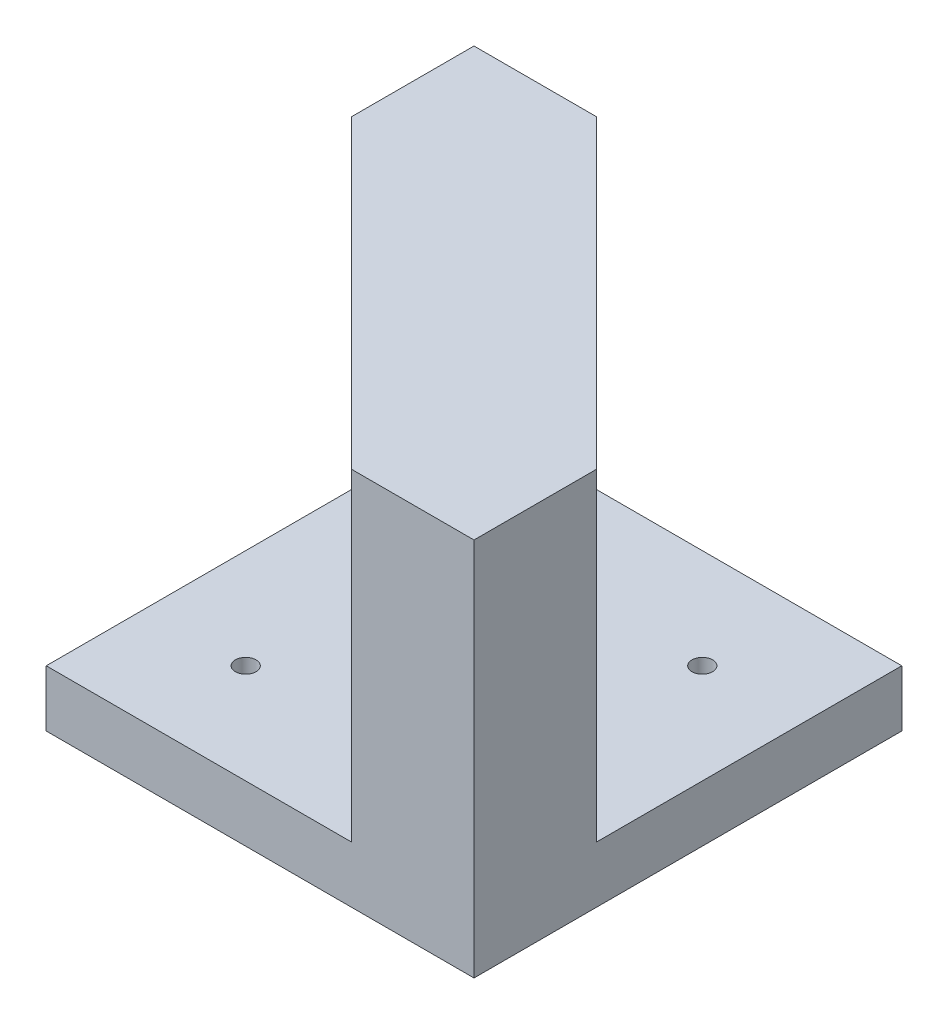
SolidWorks part; units mm, degrees
ref_plane "Front Plane" through (0, 0, 0) normal (0, 0, 1) x (1, 0, 0)
ref_plane "Top Plane" through (0, 0, 0) normal (0, 1, 0) x (1, 0, 0)
ref_plane "Right Plane" through (0, 0, 0) normal (1, 0, 0) x (0, 0, -1)
sketch "Sketch1" plane through (0, 0, 0) normal (0, 1, 0) x (1, 0, 0)
  line L1 (-33.655, 33.655) -> (33.655, 33.655)
  line L2 (-33.655, 33.655) -> (-33.655, -33.655)
  line L3 (-33.655, -33.655) -> (33.655, -33.655)
  line L4 (33.655, 33.655) -> (33.655, -33.655)
  line L5 (-33.655, 33.655) -> (33.655, -33.655) construction
  line L6 (-33.655, -33.655) -> (33.655, 33.655) construction
  circle A0 centre (17.9605, 17.9605) radius 1.625
  circle A2 centre (-17.9605, -17.9605) radius 1.625
  circle A4 centre (-17.9605, 17.9605) radius 1.625 [skipped]
  circle A5 centre (17.9605, -17.9605) radius 1.625 [skipped]
  point P0 (0, 0)
  point P6 (0, 0)
  point P7 (16.0068, 25.6922)
  point P8 (0, 0)
  point P11 (0, 0)
  point P12 (0, 0)
  point P15 (0, 0)
  point P20 (0, 0)
  dimension "D1" = 3.25
  dimension "D2" = 25.4
  dimension "D4" = 67.31
  dimension "D3" = 4
extrude "Boss-Extrude1" add sketch "Sketch1" along normal blind 8.89
sketch "Sketch2" plane through (0, 8.89, 0) normal (0, 1, 0) x (1, 0, 0)
  line L0 (-26.9233, 33.655) -> (33.655, -26.9233)
  line L1 (33.655, -26.9233) -> (33.655, -14.351)
  line L2 (33.655, -14.351) -> (-14.351, 33.655)
  line L3 (-14.351, 33.655) -> (-26.9233, 33.655)
  line L6 (26.9233, -33.655) -> (-33.655, 26.9233)
  line L8 (33.655, -33.655) -> (33.655, 33.655) construction
  line L9 (33.655, 33.655) -> (-33.655, 33.655) construction
  line L10 (-33.655, -33.655) -> (33.655, -33.655) construction
  line L11 (-33.655, 33.655) -> (-33.655, -33.655) construction
  line L12 (-33.655, 26.9233) -> (-33.655, 14.351)
  line L13 (-33.655, 14.351) -> (14.351, -33.655)
  line L14 (14.351, -33.655) -> (26.9233, -33.655)
  line L15 (-33.655, 26.9233) -> (-33.655, 33.655)
  line L16 (-33.655, 33.655) -> (-26.9233, 33.655)
  line L17 (26.9233, -33.655) -> (33.655, -33.655)
  line L18 (33.655, -33.655) -> (33.655, -26.9233)
  line M14 (33.655, -33.655) -> (33.655, 33.655)
  line M15 (33.655, 33.655) -> (-33.655, 33.655)
  line M16 (-33.655, 33.655) -> (-33.655, -33.655)
  line M17 (-33.655, -33.655) -> (33.655, -33.655)
  dimension "D1" = 45
  dimension "D2" = 8.89
  dimension "D3" = 8.89
  dimension "D4" = 27.3
extrude "Boss-Extrude2" add sketch "Sketch2" along normal blind 50.8 contours L13 L6 M16 M17 | L6 L0 M17 M14 M15 M16 | L2 L0 M14 M15 region at (6.3876, 8.89, -6.3876) region at (0, 8.89, 0) region at (-6.3876, 8.89, 6.3876)
sketch "Sketch3" plane through (-9.652, 0, 9.652) normal (-0.7071, 0, 0.7071) x (0.7071, 0, 0.7071)
  line L0 (-17.9605, 52.2505) -> (17.9605, 16.3295) construction
  line L1 (0, 8.89) -> (33.9454, 8.89) construction
  line L2 (0, 0) -> (0, 34.29) construction
  line L3 (0, 34.29) -> (-33.9454, 34.29) construction
  line L4 (-33.9454, 59.69) -> (-33.9454, 8.89) construction
  circle A0 centre (-17.9605, 52.2505) radius 2
  circle A1 centre (17.9605, 16.3295) radius 2
  circle A2 centre (0, 34.29) radius 2
  circle A3 centre (17.9605, 52.2505) radius 2
  circle A4 centre (-17.9605, 16.3295) radius 2
  point P17 (0, 0)
  dimension "4mm" = 4
  dimension "D2" = 45
  dimension "D3" = 50.8
extrude "Cut-Extrude2" cut sketch "Sketch3" against normal blind 127
